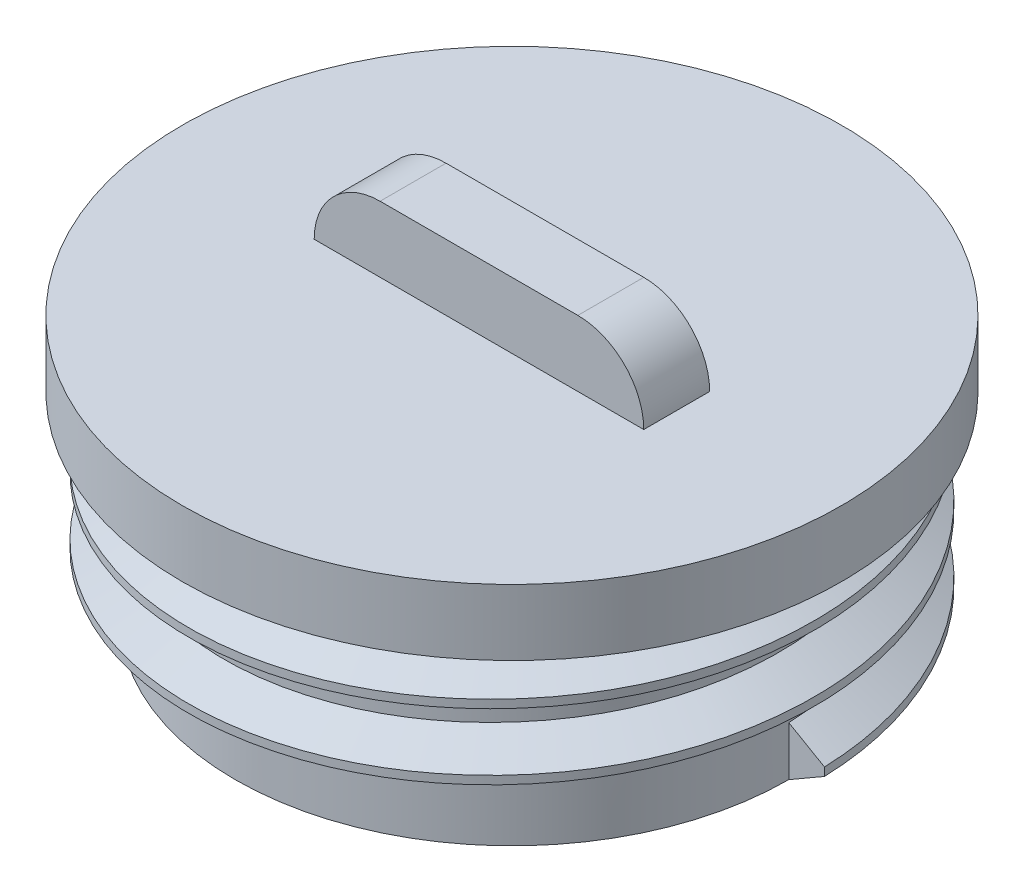
SolidWorks part; units mm, degrees
ref_plane "Front Plane" through (0, 0, 0) normal (0, 0, 1) x (1, 0, 0)
ref_plane "Top Plane" through (0, 0, 0) normal (0, 1, 0) x (1, 0, 0)
ref_plane "Right Plane" through (0, 0, 0) normal (1, 0, 0) x (0, 0, -1)
sketch "Sketch2" plane through (0, 0, 0) normal (0, 1, 0) x (1, 0, 0)
  circle A0 centre (0, 0) radius 8.4
extrude "Boss-Extrude2" add sketch "Sketch2" along normal blind 8
sketch "Sketch9" plane through (0, 8, 0) normal (0, 1, 0) x (1, 0, 0)
  circle A0 centre (0, 0) radius 10
thread "Thread2" pitch 2 method extrude profile "Thread Profile2" start angle 0, offset 0, length 0, pitch 2, diameter 16.8
ref_plane "Plane2" through (8.4, 0, 0) normal (0, 0, 1) x (1, 0, 0)
sketch "Thread Profile2" plane through (8.4, 0, 0) normal (0, 0, 1) x (1, 0, 0)
  line L0 (0, 0) -> (0, 2) construction
  line L1 (0, 0) -> (1.0825, 0.625)
  line L2 (1.0825, 0.625) -> (1.0825, 0.875)
  line L3 (1.0825, 0.875) -> (0, 1.5)
  line L4 (1.0825, 0.75) -> (0, 0.75) construction
  line L11 (0, 0) -> (0, 1.5)
  point P2 (0, 0)
  dimension "Pitch" = 2
  dimension "Profile_Angle" = 60
  dimension "Profile_Land" = 0.25
  dimension "Profile_Height" = 1.0825
sketch "Sketch12" plane through (0, 8, 0) normal (0, -1, 0) x (-1, 0, 0)
  circle A0 centre (0, 0) radius 10
ref_axis "Axis1" through (0, 8, 0) along (0, -1, 0)
extrude "Cut-Extrude1" cut sketch "Sketch12" against normal blind 10
extrude "Boss-Extrude3" add sketch "Sketch9" against normal blind 2
sketch "Sketch15" plane through (0, 8, 0) normal (0, 1, 0) x (1, 0, 0)
  line L1 (5, 0) -> (5, 1)
  line L3 (0, -1) -> (-5, -1)
  line L5 (-5, -1) -> (5, -1)
  line L6 (-5, -1) -> (-5, 1)
  line L7 (-5, 1) -> (5, 1)
  line L8 (5, -1) -> (5, 1)
  point P0 (0, 0)
extrude "Boss-Extrude4" add sketch "Sketch15" along normal blind 2 contours L5 L8 L1 L7 L6 L3 region at (0, 8, 0)
fillet "Fillet1" radius 2 2 edges at (-5, 10, 0) (5, 10, 0)
